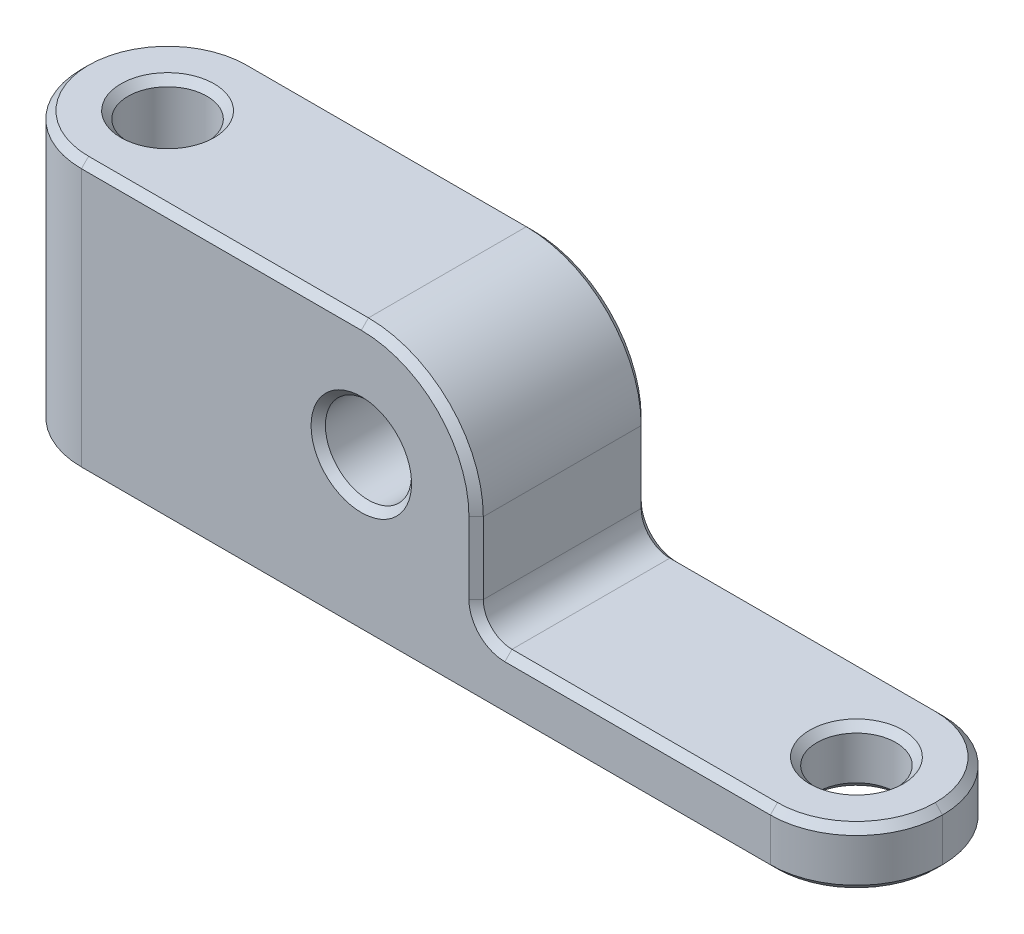
SolidWorks part; units mm, degrees
ref_plane "Front Plane" through (0, 0, 0) normal (0, 0, 1) x (1, 0, 0)
ref_plane "Top Plane" through (0, 0, 0) normal (0, 1, 0) x (1, 0, 0)
ref_plane "Right Plane" through (0, 0, 0) normal (1, 0, 0) x (0, 0, -1)
sketch "Sketch1" plane through (0, 0, 0) normal (0, 0, 1) x (1, 0, 0)
  line L0 (0, 0) -> (0, 15.0812)
  line L1 (0, 15.0812) -> (20.2406, 15.0812)
  line L2 (26.5906, 8.7312) -> (26.5906, 4.7625)
  line L3 (28.1781, 3.175) -> (47.625, 3.175)
  line L4 (47.625, 3.175) -> (47.625, 0)
  line L5 (47.625, 0) -> (0, 0)
  circle A0 centre (20.2406, 8.7312) radius 2.3813
  arc A1 (20.2406, 15.0812) -> (26.5906, 8.7312) centre (20.2406, 8.7312) cw
  arc A2 (26.5906, 4.7625) -> (28.1781, 3.175) centre (28.1781, 4.7625) ccw
  dimension "D6" = 4.7625
  dimension "D8" = 6.35
  dimension "D9" = 1.5875
  dimension "D1" = 6.35
  dimension "D2" = 47.625
  dimension "D3" = 20.2406
  dimension "D4" = 6.35
  dimension "D5" = 8.7312
  dimension "D7" = 3.175
extrude "Boss-Extrude1" add sketch "Sketch1" along normal blind 9.525
sketch "Sketch2" plane through (0, 15.0812, 0) normal (0, 1, 0) x (1, 0, 0)
  line L0 (0, -9.525) -> (0, 0) construction
  line L1 (20.2406, -9.525) -> (0, -9.525) construction
  circle A0 centre (4.7625, -4.7625) radius 2.1828
  circle A1 centre (42.8625, -4.7625) radius 2.1828
  dimension "D3" = 4.3656
  dimension "D5" = 4.3656
  dimension "D1" = 4.7625
  dimension "D2" = 4.7625
  dimension "D4" = 38.1
extrude "Cut-Extrude1" cut sketch "Sketch2" against normal through all both and the other way through all
fillet "Fillet1" radius 4.7625 4 edges at (47.625, 1.5875, 9.525) (47.625, 1.5875, 0) (0, 7.5406, 0) (0, 7.5406, 9.525)
chamfer "Chamfer1" distance 0.3969 angle 45 26 edges at (6.9453, 15.0812, 4.7625) (22.6219, 8.7312, 0) (22.6219, 8.7312, 9.525) (23.8125, 0, 0) (1.3949, 0, 1.3949) (1.3949, 0, 8.1301) (23.8125, 0, 9.525) (46.2301, 0, 8.1301) (46.2301, 0, 1.3949) (4.7625, 0, 6.9453) (1.3949, 15.0812, 1.3949) (1.3949, 15.0812, 8.1301) (12.5016, 15.0812, 0) (12.5016, 15.0812, 9.525) (24.7308, 13.2214, 0) (24.7308, 13.2214, 9.525) (26.5906, 6.7469, 0) (26.5906, 6.7469, 9.525) (27.0556, 3.64, 0) (27.0556, 3.64, 9.525) (35.5203, 3.175, 0) (46.2301, 3.175, 1.3949) (46.2301, 3.175, 8.1301) (35.5203, 3.175, 9.525) (42.8625, 0, 6.9453) (45.0453, 3.175, 4.7625)
